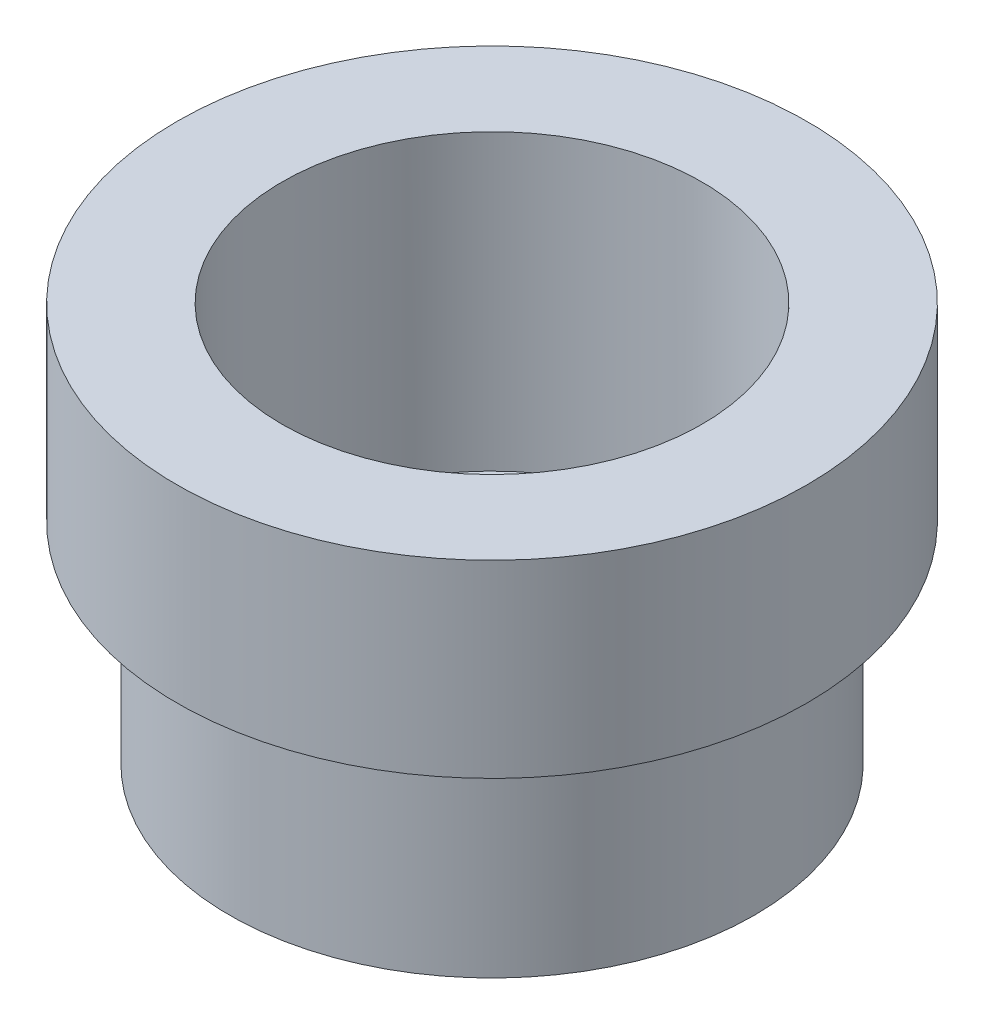
SolidWorks part; units mm, degrees
material "1060 Alloy"
ref_plane "Front" through (0, 0, 0) normal (0, 0, 1) x (1, 0, 0)
ref_plane "Top" through (0, 0, 0) normal (0, 1, 0) x (1, 0, 0)
ref_plane "Right" through (0, 0, 0) normal (1, 0, 0) x (0, 0, -1)
sketch "Sketch1" plane through (0, 0, 0) normal (0, 0, 1) x (1, 0, 0)
  line L0 (0, 0) -> (25, 0)
  line L1 (25, 0) -> (25, 20)
  line L2 (25, 20) -> (30, 20)
  line L3 (30, 20) -> (30, 38)
  line L6 (30, 38) -> (0, 38)
  line L7 (0, 38) -> (0, 0)
  dimension "D1" = 18
  dimension "D2" = 20
  dimension "D3" = 30
  dimension "D4" = 25
revolve "Revolve1" add sketch "Sketch1" angle 360 about L7
sketch "Sketch3" plane through (0, 38, 0) normal (0, 1, 0) x (1, 0, 0)
  circle A0 centre (0, 0) radius 10
  dimension "D1" = 20
extrude "bore through" cut sketch "Sketch3" against normal through all
sketch "Sketch5" plane through (0, 38, 0) normal (0, 1, 0) x (1, 0, 0)
  circle A0 centre (0, 0) radius 20
  dimension "D1" = 40
extrude "center cavity" cut sketch "Sketch5" against normal offset from surface (28 mm away) 10 up to face at (0, 0, 10)
sketch "m4 pattern alignment" plane through (0, 10, 0) normal (0, 1, 0) x (1, 0, 0)
  circle A0 centre (0, 0) radius 15 construction
  circle A1 centre (0, 15) radius 2.15
  point P3 (0, 15)
  point P4 (12.9904, 7.5)
  point P7 (12.9904, -7.5)
  point P8 (0, -15)
  point P9 (-12.9904, -7.5)
  point P10 (-12.9904, 7.5)
  point P11 (0, 0)
  dimension "D1" = 30
  dimension "D3" = 4.3
  dimension "D2" = 6
extrude "Cut-Extrude1" cut sketch "m4 pattern alignment" against normal through all
pattern_circular "CirPattern1" count 6 over 360 about axis through (0, 10, 0) along (0, -1, 0) of "Cut-Extrude1"
sketch "Sketch7" plane through (0, 10, 0) normal (0, 1, 0) x (1, 0, 0)
  circle A0 centre (0, 15) radius 4
extrude "Cut-Extrude2" cut sketch "Sketch7" against normal blind 4
pattern_circular "CirPattern2" count 6 over 360 about axis through (0, 10, 0) along (0, -1, 0) of "Cut-Extrude2"
sketch "Sketch8" plane through (0, 0, 0) normal (0, -1, 0) x (1, 0, 0)
  line L1 (0, 0) -> (-31.496, 0) construction
  line L2 (0, 0) -> (0, -31.496) construction
  line L3 (0, -31.496) -> (-31.496, -31.496) construction
  line L4 (-31.496, 0) -> (-31.496, -31.496) construction
  dimension "D1" = 31.496
  dimension "D2" = 31.496
equation "\"D1\"= \"motor mount plate thickness\""
equation "\"coupler motor shaft hole ID\"= 8mm"
equation "\"coupler OD\"= 17mm"
equation "\"coupler length\"= 25mm"
equation "\"square plate bolt pattern diameter\"= 3.5in"
equation "\"motor mount m4 screw hole diameter\"= 4mm"
equation "\"motor mount m4 head diameter\"= 7.25mm"
equation "\"motor mount m4 head depth\"= 4mm"
equation "\"motor mount plate thickness\"= 8mm + \"motor mount m4 head depth\""
equation "\"motor shaft pride\"= 32mm"
equation "\"motor mount m4 pattern diamater\"= 30mm"
equation "\"motor OD\"= 64mm"
equation "\"square plate bolt bore\"= \"m8 clearance\""
equation "\"square plate bolt head diameter\"= 13.5mm"
equation "\"motor to bearing plate distance\"= \"motor shaft pride\" + 2mm +\"coupler length\"/2"
equation "\"motor mount center bore\"= \"coupler OD\"+ 4mm"
equation "\"motor mount post radius\"= ( 3 * \"square plate bolt bore\" ) / 2"
equation "\"motor shaft diameter\"= 8mm"
equation "\"D1\"= 20mm"
equation "\"z\"= 8\t\t\t\t'number of blades"
equation "\"de\"= 0.43in\t\t\t'entrance eye diameter"
equation "\"de_length\"= 4mm\t\t'entrance eye consistent length"
equation "\"d_exit\"= 0.18in \t\t'throat aka d1"
equation "\"d2\"= 2.1in \t\t\t'outer diameter of the impeller"
equation "\"b2\"= .2in\t\t\t'tip height from disc surface at d2; slightly higher than d_exit"
equation "\"theta\"= 12\t\t\t'angle of blades from inner to outer "
equation "\"ae\"= 3.14*(\"de\"^2)/4\t\t'entrance eye area'"
equation "\"ce\"= 3.14*\"de\"\t\t'entrance eye circumference"
equation "\"av_ratio\"= .325\t\t'ratio of av/ae at N_s of 470, range is .275 to .375, .325 ideal. High ratio means bigger area means smaller blades"
equation "\"av\"= \"ae\"*\"av_ratio\"\t\t'area between just two blades"
equation "\"min blade thickness\"= .15in"
equation "\"diffuser cartridge OD\"=.75in"
equation "\"diffuser flange bolt pattern diameter\"= 1.4in"
equation "\"bearing OD\"= 30mm"
equation "\"bearing ID\"= 10mm"
equation "\"bearing depth\"= 9mm"
equation "\"bearing outer race thickness\"= 1mm"
equation "\"bearing inner race thickness\"= 1mm"
equation "\"bearing bore\"= \"bearing depth\" + 1mm"
equation "\"lower seal OD\"= .917in\t\t'this is https://www.mcmaster.com/#9281k121/=174001b"
equation "\"lower seal ID\"= .375in"
equation "\"lower seal depth\"= .625in + .218in"
equation "\"lower seal bore\"= \"lower seal depth\" + 1mm"
equation "\"upper seal OD\"= 1.125in\t'this is https://www.mcmaster.com/#5154t33/=173zuau, needs to be visually inspected before machining!"
equation "\"upper seal ID\"= 0.625in"
equation "\"upper seal depth\"= .25in\t'aka height; these values need to be confirmed by inspection!! We may want to compress the height."
equation "\"upper seal bore\"= \"upper seal depth\" + 1mm"
equation "\"big o-ring thickness\"= .139in"
equation "\"big o-ring OD\"= 2.734in"
equation "\"big o-ring ID\"= 3.012in"
equation "\"big o-ring groove depth\"= \"big o-ring thickness\"*4/5"
equation "\"impeller upper clearance\"= .5mm"
equation "\"impeller horizontal clearance\"= (\"d2\"*1.15 - \"d2\")/2 \t\t'clearance based on D2-D3 ratio for circular volute, ranges 1.15 to 1.2"
equation "\"impeller bottom clearance\"= .5mm"
equation "\"impeller base thickness\"= 2mm"
equation "\"impeller dowel diameter\"= 2mm"
equation "\"impeller bolt head depth\"= 4mm"
equation "\"impeller bolt stop depth\"= 3mm"
equation "\"impeller shaft bore depth\"= 12mm"
equation "\"impeller shaft bore\"= 8mm"
equation "\"impeller boss depth\"= \"impeller shaft bore depth\"+\"impeller bolt stop depth\"+\"impeller bolt head depth\"-\"impeller base thickness\""
equation "\"impeller boss diameter\"= \"upper seal ID\""
equation "\"impeller dowel length\"= 2mm*2 + \"impeller shaft bore\""
equation "\"square plate bolt head depth\"= 8mm"
equation "\"bearing plate stop ID\"= \"bearing OD\" - 4mm"
equation "\"bearing plate stop depth\"= 3mm"
equation "\"lower seal plate lip depth\"= 2mm"
equation "\"lower seal plate lip ID\"= \"lower seal OD\" - 3mm"
equation "\"lower seal plate thickness\"= \"lower seal plate lip depth\" + \"lower seal bore\""
equation "\"shaft coupler section diameter\"= 8mm"
equation "\"shaft coupler section length\"= \"motor to bearing plate distance\" - \"motor shaft pride\" - 2mm"
equation "\"shaft bearing section diameter\"= \"bearing ID\""
equation "\"shaft bearing section length\"= \"bearing plate stop depth\" + \"bearing depth\""
equation "\"shaft bearing stop diameter\"= \"bearing ID\" + 4mm"
equation "\"shaft bearing stop length\"= 3mm"
equation "\"shaft lower seal section diameter\"= \"lower seal ID\""
equation "\"shaft lower seal section length\"= \"lower seal plate thickness\" + 1mm"
equation "\"shaft impeller section diameter\"= \"impeller shaft bore\""
equation "\"upper seal plate lip ID\"= \"upper seal OD\" - 3mm"
equation "\"upper seal plate riser\"= 6.59mm \t\t'this number needs to be read from the housing file"
equation "\"upper seal plate pressure hole diameter\"= .125in\t'this is 1/8 drill "
equation "\"upper seal plate pressure tap diameter\"= .328125in \t'this is 21/64 drill for a 1/8 ANPT tap"
equation "\"upper seal plate pressure tap grip\"= 5mm\t\t'this is the area around the tap so it doesn't crack"
equation "\"upper seal plate pressure tap depth\"= 12mm"
equation "\"impeller cavity diameter\"= 2 * \"impeller horizontal clearance\" + \"d2\" \t\t\t\t\t\t\t\t\t'called D3 analytically"
equation "\"impeller cavity outer height\"= \"impeller bottom clearance\" + \"impeller upper clearance\" + \"impeller base thickness\" + \"b2\" \t\t'this is height at impeller diameter d2, not at d3"
equation "\"impeller housing diameter\"= 4.5in"
equation "\"impeller housing bolt count\"= 8"
equation "\"impeller housing bolt pattern diameter\"= 3.5in"
equation "\"impeller housing threaded inlet diameter\"= 0.71875in \t'this is the 23/32 drill size for 1/2 NPT fitting https://www.mcmaster.com/#50715k269/=176pljy"
equation "\"impeller housing threaded inlet depth\"= .6in"
equation "\"impeller housing exit threaded diameter\"= 0.515625in \t\t'this is the 33/64 drill size for 9/16-18 fitting, expecting swagelok SS-8FK0-1-6STH fitting"
equation "\"impeller housing exit threaded depth\"= 10mm"
equation "\"impeller housing diffuser conical angle\"=10"
equation "\"impeller housing diffuser tangent angle\"=5"
equation "\"impeller housing diffuser final diameter\"= .38in\t\t'aka d2'"
equation "\"impeller housing outlet grip\"= 5mm"
equation "\"end mill size\"= 0.375in\t'for 3/8 endmill"
equation "\"m4 clearance\"= 0.171875in \t'this is 11/64 bit for 4.36mm"
equation "\"m4 tap\"= 0.125in\t\t'this is 1/8 bit for 3.17mm"
equation "\"m4 head bore diameter\"= 7.5mm"
equation "\"m4 head bore depth\"= 5mm\t'actual is ~4mm"
equation "\"m6 clearance\"= 0.234375in\t'this is 15/64 bit = 5.95mm, could use 6mm bit, B bit for 6.04mm or 1/4 bit for 6.35mm"
equation "\"m6 tap\"= 5mm\t\t\t'5mm is appropriate, could use 13/64 or #5,6,7"
equation "\"m6 head bore diameter\"= 11mm\t\t"
equation "\"m6 head bore depth\"= 7mm\t'actual is 6mm"
equation "\"m8 clearance\"= 0.3125in\t'this is 5/16in for 7.93mm, could use 8mm, O,P, or 21/64"
equation "\"m8 tap\"= 0.265625in\t\t'this is 17/64 for 6.746875mm"
equation "\"m8 head bore diameter\"= 14mm"
equation "\"m8 head bore depth\"= 9mm\t'actual is 8mm"
